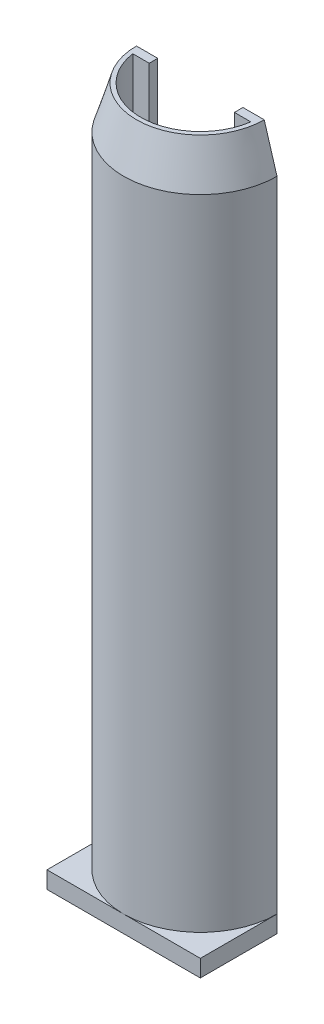
SolidWorks part; units mm, degrees
ref_plane "前视基准面" through (0, 0, 0) normal (0, 0, 1) x (1, 0, 0)
ref_plane "上视基准面" through (0, 0, 0) normal (0, 1, 0) x (1, 0, 0)
ref_plane "右视基准面" through (0, 0, 0) normal (1, 0, 0) x (0, 0, -1)
other "Configuration Table"
sketch "草图1" plane through (0, 0, 0) normal (0, 0, 1) x (1, 0, 0)
  line L0 (22.5164, 43.6428) -> (24.0164, 38.6428)
  line L1 (15.0164, 43.6428) -> (24.0164, 43.6428)
  line L2 (15.0164, 43.6428) -> (15.0164, -36.3572)
  line L3 (15.0164, -36.3572) -> (24.0164, -36.3572)
  line L4 (24.0164, 43.6428) -> (24.0164, -36.3572)
  line L5 (15.0164, 43.6428) -> (24.0164, -36.3572) construction
  line L6 (15.0164, -36.3572) -> (24.0164, 43.6428) construction
  line L7 (15.0164, 43.6428) -> (22.0164, 43.6428)
  line L8 (15.0164, 43.6428) -> (15.0164, -36.3572)
  line L9 (15.0164, -36.3572) -> (22.0164, -36.3572)
  line L10 (22.0164, 43.6428) -> (22.0164, -36.3572)
  line L11 (15.0164, 43.6428) -> (22.0164, -36.3572) construction
  line L12 (15.0164, -36.3572) -> (22.0164, 43.6428) construction
  point P0 (19.5164, 3.6428)
  point P5 (18.5164, 3.6428)
  dimension "D1" = 9
  dimension "D2" = 80
  dimension "D3" = 7
  dimension "D4" = 80
  dimension "D5" = 1.5
  dimension "D6" = 5
revolve "旋转1" add sketch "草图1" angle 180 about L2 region at (23.0044, 2.7228, 0)
sketch "草图2" plane through (0, 43.6428, 0) normal (0, 1, 0) x (1, 0, 0)
  line L5 (15.0164, -7.36) -> (15.0164, 0) construction
  line L6 (22.0164, 0) -> (20.0164, 0)
  line L7 (8.0164, 0) -> (7.5164, 0)
  line L8 (22.5164, 0) -> (22.0164, 0)
  line L9 (22.0164, 0) -> (22.0164, -1)
  line L10 (22.0164, -1) -> (20.0164, -1)
  line L11 (20.0164, 0) -> (20.0164, -1)
  arc A3 (8.0164, 0) -> (22.0164, 0) centre (15.0164, 0) ccw
  arc A4 (7.5164, 0) -> (22.5164, 0) centre (15.0164, 0) ccw
  arc A6 (7.5164, 0) -> (22.5164, 0) centre (15.0164, 0) ccw
  arc M5 (22.0164, 0) -> (8.0164, 0) centre (15.0164, 0) cw
  dimension "D1" = 2
  dimension "D2" = 1
  dimension "D3" = 5
  dimension "D5" = 0
extrude "凸台-拉伸2" add sketch "草图2" against normal blind 10 contours M5 region at (21.0046, 43.6428, 0.497)
ref_axis "基准轴1" through (15.0164, -36.3572, 0) along (0, 1, 0)
ref_plane "基准面2" through (0, -18.3572, 0) normal (0, 1, 0) x (1, 0, 0)
ref_plane "基准面4" through (0, 3.6428, 0) normal (0, 1, 0) x (1, 0, 0)
ref_plane "基准面3" through (15.0164, 0, 0) normal (1, 0, 0) x (0, 0, -1)
mirror "镜向1" about plane through (0, 3.6428, 0) normal (0, 1, 0) of "凸台-拉伸2" second plane through (15.0164, 0, 0) second plane normal (1, 0, 0)
ref_plane "基准面5" through (22.5164, 43.6428, 0) normal (1, 0, 0) x (0, 0, -1)
sketch "草图3" plane through (0, -36.3572, 0) normal (0, -1, 0) x (1, 0, 0)
  line L0 (-19.6315, -12.3407) -> (-19.6315, -0.7857) construction
  line L3 (24.0164, 0) -> (6.0164, 0)
  line L4 (24.0164, 0) -> (24.0164, 9)
  line L5 (24.0164, 9) -> (6.0164, 9)
  line L6 (6.0164, 0) -> (6.0164, 9)
  line L7 (24.0164, 0) -> (6.0164, 9) construction
  line L8 (24.0164, 9) -> (6.0164, 0) construction
  circle A1 centre (15.0164, 0) radius 7
  arc A3 (21.9446, 1) -> (8.0882, 1) centre (15.0164, 0) ccw construction
  point P5 (15.0164, 4.5)
  arc M7 (24.0164, 0) -> (6.0164, 0) centre (15.0164, 0) ccw
  line M8 (6.0164, 0) -> (10.0164, 0)
  arc M9 (8.0882, 1) -> (21.9446, 1) centre (15.0164, 0) cw
  arc M15 (8.0882, 1) -> (21.9446, 1) centre (15.0164, 0) cw
  arc M21 (8.0882, 1) -> (21.9446, 1) centre (15.0164, 0) cw
  line M22 (20.0164, 0) -> (24.0164, 0)
  dimension "D1" = 18
  dimension "D2" = 9
extrude "凸台-拉伸3" add sketch "草图3" along normal blind 2 separate body contours L6 L5 M7 | A1 M21 M22 M7 M8 M9 M15 | L4 L5 M7 region at (22.0061, -36.3572, 6.9897) region at (23.0164, -36.3572, 0.2012) region at (8.0267, -36.3572, 6.9897)
